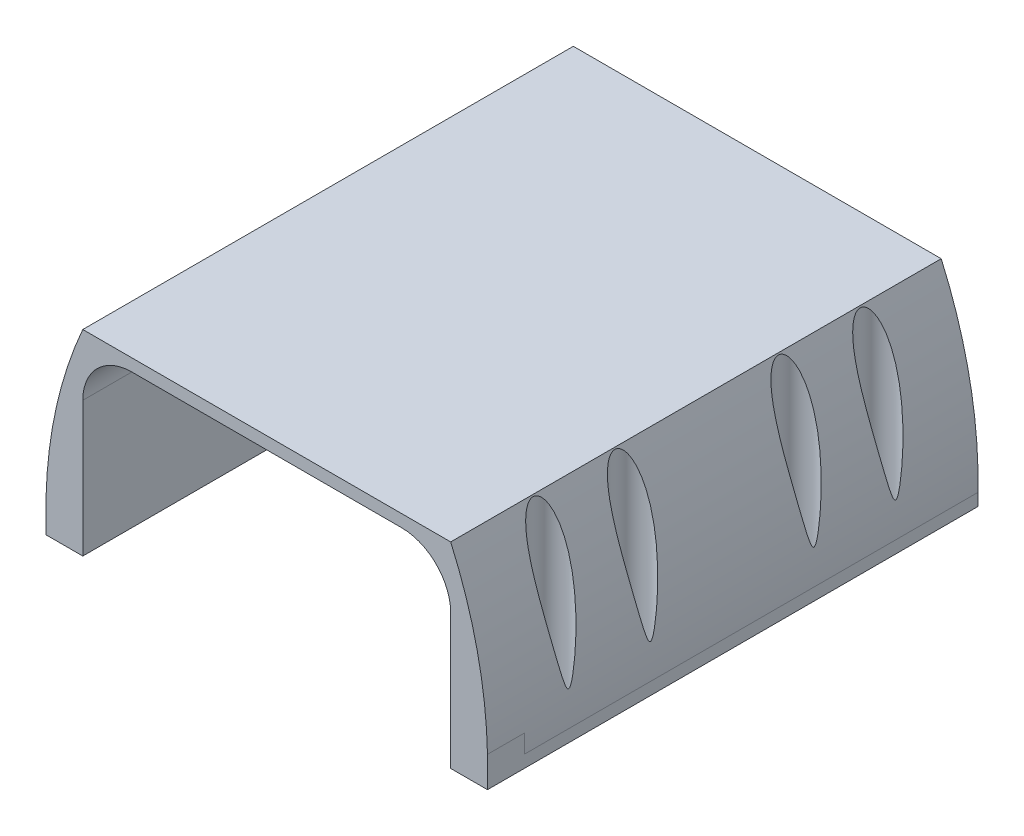
SolidWorks part; units mm, degrees
ref_plane "Front Plane" through (0, 0, 0) normal (0, 0, 1) x (1, 0, 0)
ref_plane "Top Plane" through (0, 0, 0) normal (0, 1, 0) x (1, 0, 0)
ref_plane "Right Plane" through (0, 0, 0) normal (1, 0, 0) x (0, 0, -1)
sketch "Sketch1" plane through (0, 0, 0) normal (0, 1, 0) x (1, 0, 0)
  line L0 (0, 0) -> (0.1479, 0) construction
  line L1 (0, 0) -> (0, 0.1142) construction
  line L2 (-82.5, 66.6667) -> (-82.5, 100) construction
  line L3 (-75, 85) -> (75, 85)
  line L4 (-75, 85) -> (-75, -85)
  line L5 (-75, -85) -> (75, -85)
  line L6 (75, 85) -> (75, -85)
  line L7 (-90, 100) -> (90, 100)
  line L8 (-90, 100) -> (-90, -100)
  line L9 (-90, -100) -> (90, -100)
  line L10 (90, 100) -> (90, -100)
  line L51 (-82.5, 33.3333) -> (-82.5, 0) construction
  line L52 (-82.5, 66.6667) -> (-82.5, 33.3333) construction
  circle A4 centre (-82.5, 33.3333) radius 3.25
  circle A5 centre (-82.5, 66.6667) radius 3.25
  circle A7 centre (-82.5, 66.6667) radius 7.5
  circle A8 centre (-82.5, 33.3333) radius 7.5
  circle A9 centre (82.5, 33.3333) radius 7.5
  circle A10 centre (82.5, 33.3333) radius 3.25
  circle A11 centre (82.5, 66.6667) radius 3.25
  circle A12 centre (82.5, 66.6667) radius 7.5
  circle A13 centre (82.5, -33.3333) radius 3.25
  circle A14 centre (82.5, -33.3333) radius 7.5
  circle A15 centre (82.5, -66.6667) radius 7.5
  circle A16 centre (82.5, -66.6667) radius 3.25
  circle A17 centre (-82.5, -33.3333) radius 3.25
  circle A18 centre (-82.5, -33.3333) radius 7.5
  circle A19 centre (-82.5, -66.6667) radius 3.25
  circle A20 centre (-82.5, -66.6667) radius 7.5
  point P59 (-90, -100)
  point P64 (90, 100)
  dimension "D1" = 6.5
  dimension "D2" = 6.5
  dimension "D3" = 15
  dimension "D5" = 200
  dimension "D6" = 180
  dimension "D8" = 15
extrude "Boss-Extrude11" add sketch "Sketch1" along normal blind 80 contours L3 L6 L5 L4
extrude "Boss-Extrude13" add sketch "Sketch1<17>" along normal blind 5 contours L4 A20 L8 L9 L10 A15 L6 L5 | A15 L10 A14 L6 | A14 L10 A9 L6 | L10 A12 L6 A9 | L6 A12 L10 L7 L8 A7 L4 L3 | L8 A20 L4 A18 | L8 A18 L4 A8 | A8 L4 A7 L8 | A20 A19 | A18 A17 | A8 A4 | A7 A5 | A15 A16 | A14 A13 | A9 A10 | A12 A11 region at (0, 0, -90.8197) region at (-82.5, 0, -59.3788) region at (-82.5, 0, -50) region at (82.5, 0, -50) region at (82.5, 0, -73.9545) region at (-82.5, 0, -26.0455) region at (-82.5, 0, 0) region at (82.5, 0, 0) region at (82.5, 0, -40.6212) region at (-82.5, 0, 40.6212) region at (-82.5, 0, 50) region at (82.5, 0, 50) region at (82.5, 0, 26.0455) region at (-82.5, 0, 73.9545) region at (0, 0, 90.8197) region at (82.5, 0, 59.3788)
sketch "Sketch1<17>" plane through (0, 0, 0) normal (0, 1, 0) x (1, 0, 0) same geometry as "Sketch1"
sketch "Sketch33" plane through (0, 5, 0) normal (0, 1, 0) x (1, 0, 0)
  line L0 (75, -85) -> (90, -100)
  point P4 (0, 0)
sketch "Sketch34" plane through (75, 0, 0) normal (1, 0, 0) x (0, 0, -1)
  line L0 (-85, 80) -> (-85, 5)
  line L1 (-85, 5) -> (-100, 5) construction
  line L2 (-85, 80) -> (-85, 5) construction
sketch "Sketch35" plane through (0, 0, 85) normal (0, 0, 1) x (1, 0, 0)
  line L0 (75, 5) -> (90, 5) construction
  line L1 (75, 80) -> (75, 5) construction
  line L2 (75, 5) -> (90, 5)
  line L3 (75, 80) -> (75, 5)
sketch "Sketch37" plane through (0, 0, 85) normal (0, 0, 1) x (1, 0, 0)
  line L0 (75, 80) -> (75, 5) construction
  line L1 (75, 5) -> (90, 5) construction
  line L2 (75, 80) -> (75, 5)
  line L3 (75, 5) -> (90, 5)
  arc A3 (75, 80) -> (90, 5) centre (-86.2698, 8.746) cw
sketch "Sketch42" plane through (0, 5, 0) normal (0, 1, 0) x (1, 0, 0)
  line L0 (75, -85) -> (90, -100)
  line L1 (90, -100) -> (90, -85)
  line L2 (75, -85) -> (90, -85) construction
  line L3 (90, 100) -> (90, -100) construction
  line L4 (90, -85) -> (75, -85)
sketch "Sketch49" plane through (0, 0, 85) normal (0, 0, 1) x (1, 0, 0)
  line L0 (-75, 5) -> (75, 5)
sketch "Sketch50" plane through (-75, 0, 0) normal (-1, 0, 0) x (0, 0, 1)
  line L0 (-85, 5) -> (85, 5)
sketch "Sketch52" plane through (75, 0, 0) normal (1, 0, 0) x (0, 0, -1)
  line L0 (-85, 5) -> (85, 5)
sketch "Sketch53" plane through (0, 5, 0) normal (0, 1, 0) x (1, 0, 0)
  line L1 (0, -85) -> (0, 95.7142) construction
  line L2 (0, -200000) -> (0, 200000.1142) construction
  line L3 (-44, 0) -> (44, 0) construction
  circle A1 centre (-82.5, -66.6667) radius 7.25
  circle A3 centre (-82.5, -33.3333) radius 7.25
  circle A6 centre (82.5, -66.6667) radius 7.25
  circle A7 centre (82.5, -33.3333) radius 7.25
  circle A8 centre (-82.5, 33.3333) radius 7.25
  circle A9 centre (-82.5, 66.6667) radius 7.25
  circle A10 centre (82.5, 66.6667) radius 7.25
  circle A11 centre (82.5, 33.3333) radius 7.25
  dimension "D1" = 14.5
extrude "Boss-Extrude19" add sketch "Sketch37" against normal up to vertex (185 mm away) contours A3 L3 L2 up to point (90, 5, -100)
mirror "Mirror3" about plane through (0, 0, 0) normal (1, 0, 0) of "Boss-Extrude19"
extrude "Cut-Extrude5" cut sketch "Sketch53" along normal blind 184 contours A1
sketch "Sketch56" plane through (0, 5, 0) normal (0, 1, 0) x (1, 0, 0)
  circle A0 centre (-82.5, -33.3333) radius 7.25
  point P2 (-82.5, -33.3333)
  dimension "D1" = 14.5
extrude "Cut-Extrude6" cut sketch "Sketch53<5>" along normal blind 184
sketch "Sketch53<5>" plane through (0, 5, 0) normal (0, 1, 0) x (1, 0, 0) same geometry as "Sketch53"
sketch "Sketch58" plane through (0, 5, 0) normal (0, 1, 0) x (1, 0, 0)
  line L1 (-90.0398, -85) -> (90, -85)
  line L2 (-90.0398, -85) -> (-90.0398, -100)
  line L3 (-90.0398, -100) -> (90, -100)
  line L4 (90, -85) -> (90, -100)
  point P6 (0, 0)
sketch "Sketch62" plane through (0, 5, 0) normal (0, 1, 0) x (1, 0, 0)
  line L1 (-75, 100) -> (75, 100)
  line L2 (-75, 100) -> (-75, 85)
  line L3 (-75, 85) -> (75, 85)
  line L4 (75, 100) -> (75, 85)
extrude "Boss-Extrude20" add sketch "Sketch62" along normal up to vertex (75 mm away) up to point (-75, 80, -85)
sketch "Sketch63" plane through (0, 0, 85) normal (0, 0, 1) x (1, 0, 0)
  line L0 (-75, 80) -> (75, 80) construction
  line L1 (75, 5) -> (-75, 5)
  line L2 (75, 5) -> (75, 65)
  line L3 (65, 75) -> (-65, 75)
  line L4 (-75, 5) -> (-75, 65)
  arc A0 (75, 65) -> (65, 75) centre (65, 65) ccw
  arc A1 (-65, 75) -> (-75, 65) centre (-65, 65) ccw
  point P7 (0, 0)
  dimension "D2" = 10
  dimension "D1" = 5
sketch "Sketch67" plane through (0, 0, 85) normal (0, 0, 1) x (1, 0, 0)
  line L0 (-75, 80) -> (75, 80)
  line L3 (-90, 5) -> (-90, 0)
  line L4 (-90, 0) -> (90, 0)
  line L5 (90, 12.4921) -> (90, 0)
  arc A0 (-75, 80) -> (-90, 5) centre (86.2698, 8.746) ccw
  arc A1 (-75, 80) -> (-90, 5) centre (86.2698, 8.746) ccw construction
  arc A2 (75, 80) -> (90, 12.4921) centre (-86.2698, 8.746) cw
  arc A4 (90, 5) -> (75, 80) centre (-86.2698, 8.746) ccw construction
extrude "Boss-Extrude21" add sketch "Sketch67" along normal up to vertex (15 mm away) up to point (-90, 5, 100)
sketch "Sketch68" plane through (0, 0, 100) normal (0, 0, 1) x (1, 0, 0)
  line L0 (-90, 0) -> (90, 0) construction
  line L1 (-75, 0) -> (75, 0)
  line L2 (-75, 0) -> (-75, 55)
  line L3 (-55, 75) -> (55, 75)
  line L4 (75, 0) -> (75, 55)
  line L5 (75, 80) -> (75, 5) construction
  line L9 (-75, 5) -> (-75, 65) construction
  line L10 (65, 75) -> (-65, 75) construction
  arc A0 (-75, 55) -> (-55, 75) centre (-55, 55) cw
  arc A1 (55, 75) -> (75, 55) centre (55, 55) cw
  point P16 (75, 75)
  dimension "D1" = 20
  dimension "D2" = 20
extrude "Cut-Extrude10" cut sketch "Sketch68" against normal offset from surface (185 mm away) 15 up to face at (0, 28.6077, -100)
